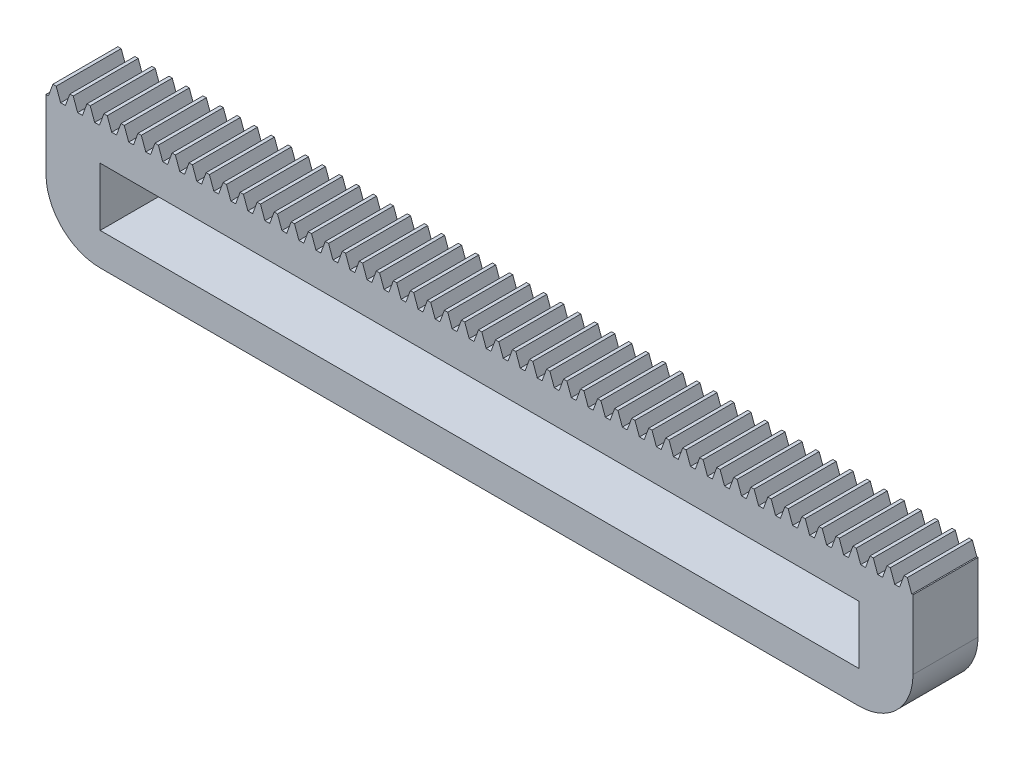
SolidWorks part; units mm, degrees
extrude "Blank" add sketch "BlankSke" against normal blind 6
sketch "BlankSke" plane through (0, 0, 0) normal (0, 0, 1) x (1, 0, 0)
  line L1 (0, 0) -> (80, 0)
  line L2 (0, 0) -> (0, 12.5)
  line L3 (0, 12.5) -> (80, 12.5)
  line L4 (80, 0) -> (80, 12.5)
  dimension "Length" = 80
ref_plane "Plane1" through (0, 0, 0) normal (0, 0, 1) x (1, 0, 0)
ref_plane "Plane2" through (0, 0, 0) normal (0, 1, 0) x (1, 0, 0)
ref_plane "Plane3" through (0, 0, 0) normal (1, 0, 0) x (0, 0, -1)
sketch "HoldingSke" plane through (0, 0, 0) normal (0, 1, 0) x (1, 0, 0)
  line L0 (0, 0) -> (0.2783, 1.9805)
  line L1 (-15, 0) -> (100, 0) construction
  line L2 (0, 0) -> (-2.1039, 2.3779)
  line L3 (0, 0) -> (-11.863, 4.5341)
  line L4 (0, 0) -> (-5.4348, 6.7114)
  line L5 (0, 0) -> (-23.7986, -8.8762)
  line L6 (0, 0) -> (-10.5278, -7.1032)
  line L9 (-71.009, 38.7566) -> (116.9296, 107.1606)
  line L10 (-76.2, 2.8779) -> (-64.2, 2.8779)
  line L11 (0, 0) -> (-6, 0)
  line L12 (-76.2, 101.6) -> (-76.181, 101.6)
  line L13 (24.9733, 27.94) -> (52.9518, 28.4284)
  line L14 (24.9733, 27.94) -> (24.9743, 27.94)
  line L15 (24.9733, 27.94) -> (100.4006, 29.5858)
  circle A0 centre (0, 0) radius 19.05
  circle A1 centre (0, 0) radius 6
  circle A2 centre (0, 0) radius 12.7
  dimension "Num_teeth" = 129
  dimension "Width" = 6
  dimension "Pitch_height" = 12
sketch "TooCutSkeIll" plane through (0, 0, 0) normal (0, 0, 1) x (1, 0, 0)
  line L0 (-0.6269, 12.4868) -> (-0.2524, 11.4579)
  line L1 (-0.134, 11.375) -> (0.134, 11.375)
  line L2 (0.2524, 11.4579) -> (0.6269, 12.4868)
  line L3 (80, 12.5) -> (0, 12.5) construction
  line L4 (0, 0) -> (0, 64.897) construction
  line L5 (-13.208, 12) -> (12.954, 12) construction
  line L6 (0, 0) -> (80, 0) construction
  line L7 (0.4497, 12) -> (0.4497, 48.7463) construction
  line L8 (-0.4497, 12) -> (-0.4497, 48.7463) construction
  line L9 (0.6457, 12.5) -> (0.6457, 12.5254)
  line L10 (-0.6457, 12.5) -> (-0.6457, 12.5254)
  line L11 (-0.6457, 12.5254) -> (0.6457, 12.5254)
  arc A0 (0.134, 11.375) -> (0.2524, 11.4579) centre (0.134, 11.501) ccw
  arc A1 (-0.2524, 11.4579) -> (-0.134, 11.375) centre (-0.134, 11.501) ccw
  arc A2 (0.6457, 12.5) -> (0.6269, 12.4868) centre (0.6457, 12.48) ccw
  arc A3 (-0.6269, 12.4868) -> (-0.6457, 12.5) centre (-0.6457, 12.48) ccw
  dimension "Addendum_plus" = 0.5254
  dimension "Pitch_height" = 12
  dimension "Pressure_angle" = 20
  dimension "Gap_width" = 0.8994
  dimension "Dedendum" = 0.625
extrude "ToothCutIll" [suppressed] cut sketch "TooCutSkeIll" against normal through all
sketch "TooCutSkeSim" plane through (0, 0, 0) normal (0, 0, 1) x (1, 0, 0)
  line L0 (0.2222, 11.375) -> (-0.2222, 11.375)
  line L1 (0.6409, 12.5254) -> (0.2222, 11.375)
  line L2 (0, 17.4625) -> (0, 53.467) construction
  line L3 (0.6409, 12.5254) -> (-0.6409, 12.5254)
  line L6 (-0.6409, 12.5254) -> (-0.2222, 11.375)
  line L9 (-0.4497, 12) -> (0.4497, 12) construction
  line L10 (0, 0) -> (80, 0) construction
  line L11 (0.4497, 12) -> (0.4497, 53.467) construction
  line L12 (-0.4497, 12) -> (-0.4497, 53.467) construction
  dimension "Addendum_plus" = 0.5254
  dimension "Pitch_height" = 12
  dimension "Pressure_angle" = 20
  dimension "Gap_width" = 0.8994
  dimension "Dedendum" = 0.625
extrude "ToothCutSim" cut sketch "TooCutSkeSim" against normal through all
pattern_linear "TeethCuts" count 129 spacing 1.5708 along (1, 0, 0) of "ToothCutIll", "ToothCutSim"
sketch "Sketch1" plane through (0, 0, 0) normal (0, -1, 0) x (1, 0, 0)
  line L1 (0, 0) -> (80, 0)
  line L2 (0, 0) -> (0, -6)
  line L3 (0, -6) -> (80, -6)
  line L4 (80, 0) -> (80, -6)
extrude "Boss-Extrude1" add sketch "Sketch1" along normal blind 10
ref_plane "Plane5" through (0, -10, 0) normal (0, -1, 0) x (-1, 0, 0)
mirror "Mirror1" [suppressed] about plane through (0, -10, 0) normal (0, -1, 0)
fillet "Fillet2" [suppressed] radius 20
sketch "Sketch4" plane through (0, 0, 0) normal (0, 0, 1) x (1, 0, 0)
  line L1 (-2.9931, 0) -> (85.891, 0)
  line L2 (-2.9931, 0) -> (-2.9931, -15.472)
  line L3 (-2.9931, -15.472) -> (85.891, -15.472)
  line L4 (85.891, 0) -> (85.891, -15.472)
extrude "Cut-Extrude3" cut sketch "Sketch4" against normal through all
sketch "Sketch3" plane through (0, 0, 0) normal (0, 0, 1) x (1, 0, 0)
  line L0 (0, 5.6875) -> (80, 5.6875) construction
  line L1 (80, 0) -> (0, 0) construction
  line L2 (0, 11.375) -> (0, 0) construction
  line L7 (80, 0) -> (80, 11.375) construction
  line L9 (5, 3) -> (75, 3)
  line L10 (5, 3) -> (5, 8.375)
  line L11 (5, 8.375) -> (75, 8.375)
  line L12 (75, 3) -> (75, 8.375)
  line L13 (5, 3) -> (75, 8.375) construction
  line L14 (5, 8.375) -> (75, 3) construction
  point P5 (40, 0)
  point P8 (40, 5.6875)
  dimension "D1" = 5
  dimension "D2" = 3
extrude "Cut-Extrude2" cut sketch "Sketch3" against normal blind 10
fillet "Fillet3" radius 5 2 edges at (80, 0, -3) (0, 0, -3)
equation "' \"Module@HoldingSke\" = 6.35"
equation "' \"Num_teeth@HoldingSke\" = 12"
equation "' \"Ap@HoldingSke\" =  20"
equation "' \"Ap@HoldingSke\" = 20"
equation "' \"Width@HoldingSke\" = 0.25 * 25.4"
equation "' \"Show_teeth@HoldingSke\" = 500"
equation "' \"Backlash@HoldingSke\" = 0.009 * 25.4"
equation "' \"Addendum_fac@HoldingSke\" = 1.0"
equation "' \"Dedendum_fac@HoldingSke\" = 1.25"
equation "' \"Dedendum_add@HoldingSke\" = 0.00005 * 25.4"
equation "' \"Clearance_fac@HoldingSke\" = 0.25"
equation "' \"Pitch_height@HoldingSke\" = 1 * 25.4"
equation "' \"Length@HoldingSke\" = 4.71 * 25.4"
equation "\"Pitch@HoldingSke\" = 1 / \"Module@HoldingSke\""
equation "\"MPH@HoldingSke\" = \"Dedendum_fac@HoldingSke\" / \"Pitch@HoldingSke\" + 2 * \"Dedendum_add@HoldingSke\" + 0.002 * 25.4"
equation "\"MPH@HoldingSke\" = ((sgn( \"MPH@HoldingSke\" - \"Pitch_height@HoldingSke\")+1)*( \"MPH@HoldingSke\" - \"Pitch_height@HoldingSke\"))/2 + \"Pitch_height@HoldingSke\""
equation "\"Blank_height@BlankSke\" = \"Pitch_height@HoldingSke\" + \"Addendum_fac@HoldingSke\"  / \"Pitch@HoldingSke\" "
equation "\"Length@BlankSke\"=80"
equation "\"Face_width@Blank\" = \"Width@HoldingSke\""
equation "\"Pressure_angle@TooCutSkeIll\" = \"Ap@HoldingSke\""
equation "\"Addendum_plus@TooCutSkeIll\" =  \"Addendum_fac@HoldingSke\"  / \"Pitch@HoldingSke\" + 0.001 *25.4"
equation "\"Dedendum@TooCutSkeIll\" = \"Dedendum_fac@HoldingSke\"  / \"Pitch@HoldingSke\""
equation "\"Pitch_height@TooCutSkeIll\" =  \"MPH@HoldingSke\""
equation "\"Gap_width@TooCutSkeIll\" = 3.14159265 / 2 / \"Pitch@HoldingSke\" + 6 * \"Backlash@HoldingSke\""
equation "\"Pressure_angle@TooCutSkeSim\" = \"Ap@HoldingSke\""
equation "\"Addendum_plus@TooCutSkeSim\" =  \"Addendum_fac@HoldingSke\"  / \"Pitch@HoldingSke\" + 0.001 * 25.4"
equation "\"Dedendum@TooCutSkeSim\" = \"Dedendum_fac@HoldingSke\"  / \"Pitch@HoldingSke\""
equation "\"Pitch_height@TooCutSkeSim\" =  \"MPH@HoldingSke\""
equation "\"Gap_width@TooCutSkeSim\" = 3.14159265 / 2 / \"Pitch@HoldingSke\" + 6 * \"Backlash@HoldingSke\""
equation "\"Root_fillet@TooCutSkeIll\" = \"Clearance_fac@HoldingSke\" / \"Pitch@HoldingSke\" + \"Dedendum_add@HoldingSke\""
equation "\"Break_rad@TooCutSkeIll\" = 0.02 / \"Pitch@HoldingSke\" * 2"
equation "\"Linear_pitch@TeethCuts\" = 3.14159265 / \"Pitch@HoldingSke\""
equation "\"Num_teeth@HoldingSke\" = int( ( \"Length@HoldingSke\" + 0 ) / (3.14159265 / \"Pitch@HoldingSke\")) + 0.9999  + 1"
equation " \"Num_teeth@TeethCuts\" = int( \"Show_teeth@HoldingSke\" ) + 1"
equation " \"Num_teeth@TeethCuts\" = ((sgn( \"Num_teeth@TeethCuts\" - \"Num_teeth@HoldingSke\" )-1)*( \"Num_teeth@TeethCuts\" - \"Num_teeth@HoldingSke\" ))/-2+ \"Num_teeth@HoldingSke\""
equation " \"Num_teeth@TeethCuts\" = ((sgn( \"Num_teeth@TeethCuts\" - 2.0)+1)*( \"Num_teeth@TeethCuts\" - 2.0))/2 +2.0"
